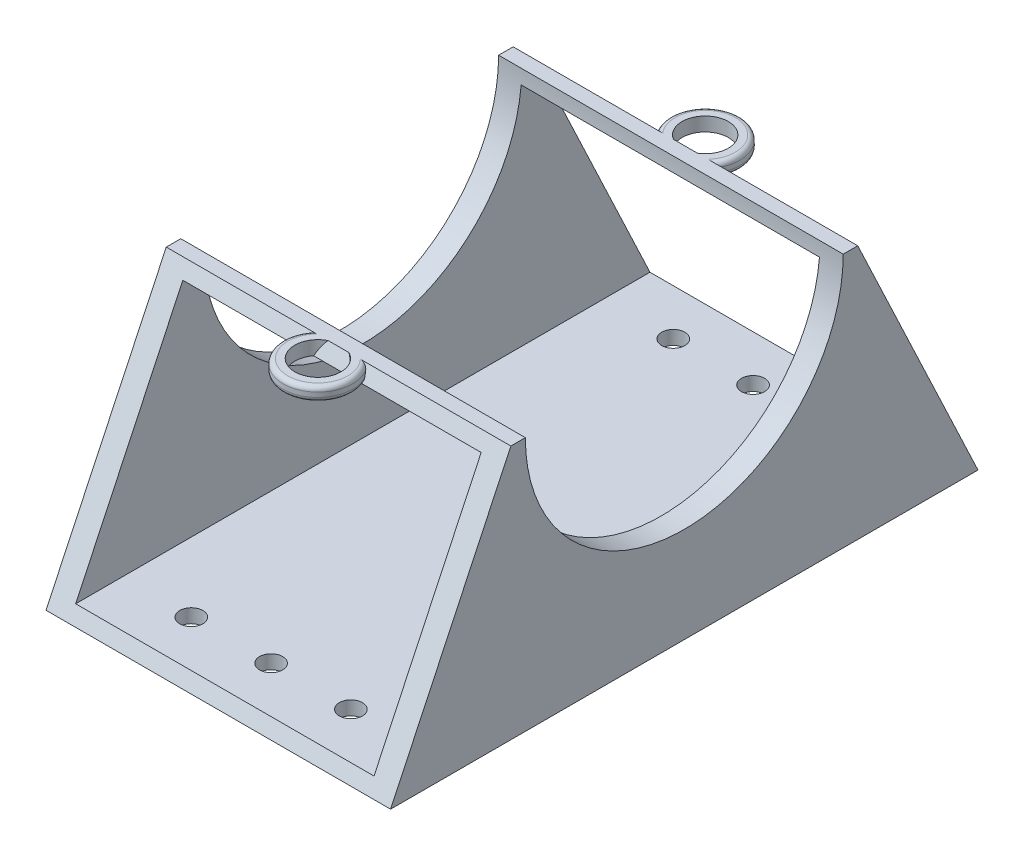
SolidWorks part; units mm, degrees
ref_plane "Front Plane" through (0, 0, 0) normal (0, 0, 1) x (1, 0, 0)
ref_plane "Top Plane" through (0, 0, 0) normal (0, 1, 0) x (1, 0, 0)
ref_plane "Right Plane" through (0, 0, 0) normal (1, 0, 0) x (0, 0, -1)
sketch "Sketch1" plane through (0, 0, 0) normal (0, 1, 0) x (1, 0, 0)
  line L1 (-37.25, -37.5) -> (37.25, -37.5)
  line L2 (-37.25, -37.5) -> (-37.25, 37.5)
  line L3 (-37.25, 37.5) -> (37.25, 37.5)
  line L4 (37.25, -37.5) -> (37.25, 37.5)
  line L5 (-37.25, -37.5) -> (37.25, 37.5) construction
  line L6 (-37.25, 37.5) -> (37.25, -37.5) construction
  point P0 (0, 0)
  dimension "D1" = 74.5
  dimension "D2" = 75
extrude "Boss-Extrude1" add sketch "Sketch1" along normal blind 55
ref_plane "Plane1" through (0, 0, -37.5) normal (0, 0, -1) x (-1, 0, 0)
ref_plane "Plane2" through (0, 0, 37.5) normal (0, 0, 1) x (1, 0, 0)
ref_plane "Plane3" through (-37.25, 0, 0) normal (-1, 0, 0) x (0, 0, 1)
ref_plane "Plane4" through (37.25, 0, 0) normal (1, 0, 0) x (0, 0, -1)
sketch "Sketch5" plane through (37.25, 0, 0) normal (1, 0, 0) x (0, 0, -1)
  line L1 (-37.5, 55) -> (37.5, 55) construction
  circle A0 centre (0, 55) radius 34.3616
  dimension "D1" = 68.7231
extrude "Cut-Extrude2" cut sketch "Sketch5" against normal through all
sketch "Sketch7" plane through (37.25, 0, 0) normal (1, 0, 0) x (0, 0, -1)
  line L0 (-37.5, 55) -> (-63.5, 0)
  line L1 (-63.5, 0) -> (-37.5, 0)
  line L2 (-37.5, 0) -> (-37.5, 55)
  dimension "D1" = 26
extrude "Boss-Extrude3" add sketch "Sketch7" against normal blind 74.5
sketch "Sketch8" plane through (37.25, 0, 0) normal (1, 0, 0) x (0, 0, -1)
  line L0 (37.5, 55) -> (63.5, 0)
  line L1 (63.5, 0) -> (37.5, 0)
  line L2 (37.5, 0) -> (37.5, 55)
  dimension "D1" = 26
extrude "Boss-Extrude4" add sketch "Sketch8" against normal blind 74.5
sketch "Sketch9" plane through (0, 0, 37.5) normal (0, 0, 1) x (1, 0, 0)
  line L0 (-37.25, 55) -> (37.25, 55) construction
  line L1 (-32.25, 3) -> (32.25, 3)
  line L2 (-32.25, 3) -> (-32.25, 52)
  line L3 (-32.25, 52) -> (32.25, 52)
  line L4 (32.25, 3) -> (32.25, 52)
  line L5 (-32.25, 3) -> (32.25, 52) construction
  line L6 (-32.25, 52) -> (32.25, 3) construction
  line L7 (-37.25, 0) -> (37.25, 0) construction
  line L8 (37.25, 55) -> (37.25, 0) construction
  line L9 (-37.25, 55) -> (-37.25, 0) construction
  point P0 (0, 27.5)
  dimension "D1" = 3
  dimension "D2" = 3
  dimension "D3" = 5
  dimension "D4" = 5
extrude "Cut-Extrude3" cut sketch "Sketch9" against normal through all both and the other way through all
sketch "Sketch10" plane through (0, 55, 0) normal (0, 1, 0) x (1, 0, 0)
  circle A0 centre (0, 41.7725) radius 7.5
  circle A1 centre (0, 41.7725) radius 5
  line M4 (37.25, 37.5) -> (-37.25, 37.5)
  dimension "D1" = 15
  dimension "D2" = 10
extrude "Boss-Extrude5" add sketch "Sketch10" against normal blind 3 contours A1 A0 M4 region at (6.9762, 55, -39.5912)
sketch "Sketch11" plane through (0, 55, 0) normal (0, 1, 0) x (1, 0, 0)
  circle A0 centre (0, -41.9683) radius 7.5
  circle A1 centre (0, -41.9683) radius 5
  line M10 (-37.25, -37.5) -> (37.25, -37.5)
  dimension "D1" = 15
  dimension "D2" = 10
extrude "Boss-Extrude6" add sketch "Sketch11" against normal blind 3 contours A1 A0 M10 region at (-2.2927, 55, 48.9075)
fillet "Fillet1" radius 1 4 edges at (0, 52, 49.4683) (0, 55, 49.4683) (0, 52, -49.2725) (0, 55, -49.2725)
sketch "Sketch12" plane through (0, 3, 0) normal (0, 1, 0) x (1, 0, 0)
  line L0 (-32.25, 62.0818) -> (-32.25, -62.0818) construction
  line L1 (32.25, 62.0818) -> (32.25, -62.0818) construction
  line L2 (-32.25, -62.0818) -> (32.25, -62.0818) construction
  circle A0 centre (-17.25, -52.0818) radius 2.5
  circle A1 centre (17.25, -52.0818) radius 2.5
  circle A2 centre (0, -52.0818) radius 2.5
  dimension "D1" = 5
  dimension "D3" = 5
  dimension "D4" = 15
  dimension "D5" = 10
  dimension "D6" = 10
  dimension "D7" = 5
  dimension "D8" = 10
  dimension "D9" = 17.25
  dimension "D2" = 15
extrude "Cut-Extrude4" cut sketch "Sketch12" against normal through all
pattern_linear "LPattern1" count 2 spacing 104.2 along (0, 0, -1) of "Cut-Extrude4"
